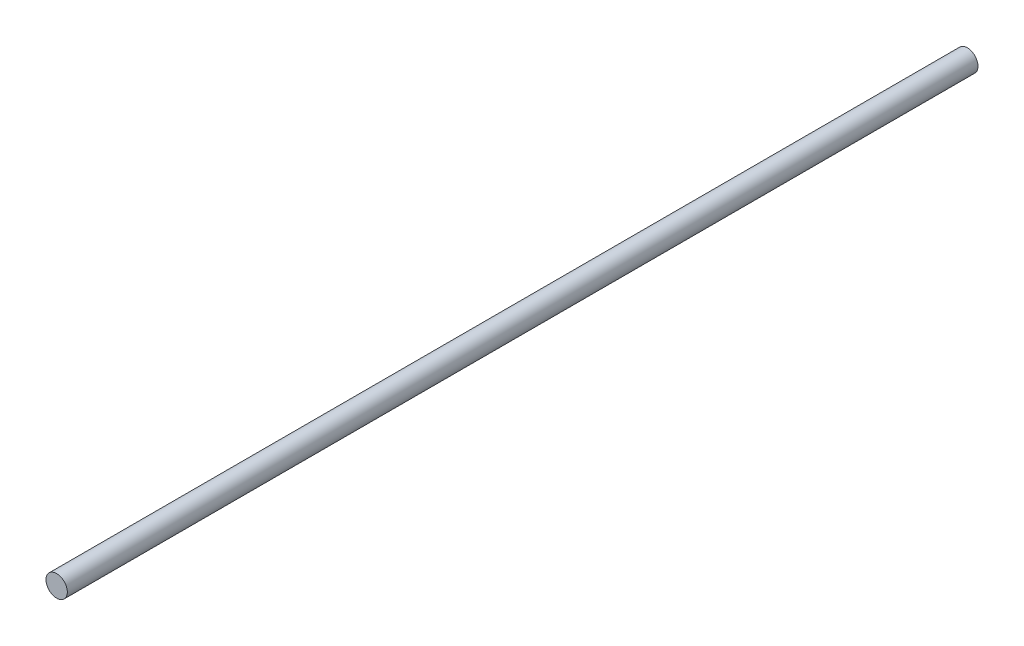
SolidWorks part; units mm, degrees
material "AISI 304"
ref_plane "Front Plane" through (0, 0, 0) normal (0, 0, 1) x (1, 0, 0)
ref_plane "Top Plane" through (0, 0, 0) normal (0, 1, 0) x (1, 0, 0)
ref_plane "Right Plane" through (0, 0, 0) normal (1, 0, 0) x (0, 0, -1)
sketch "Sketch1" plane through (0, 0, 0) normal (0, 0, 1) x (1, 0, 0)
  circle A0 centre (0, 0) radius 3
  dimension "D1" = 6
extrude "Boss-Extrude1" add sketch "Sketch1" along normal blind 256
